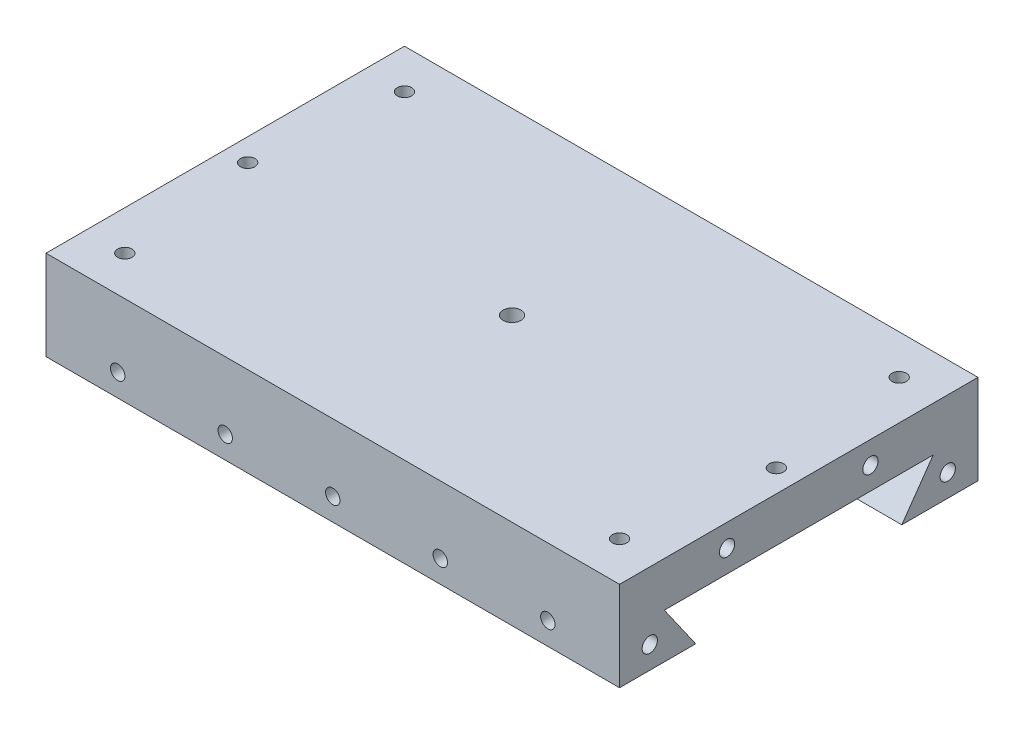
SolidWorks part; units mm, degrees
material "Ductile Iron"
ref_plane "Front Plane" through (0, 0, 0) normal (0, 0, 1) x (1, 0, 0)
ref_plane "Top Plane" through (0, 0, 0) normal (0, 1, 0) x (1, 0, 0)
ref_plane "Right Plane" through (0, 0, 0) normal (1, 0, 0) x (0, 0, -1)
sketch "Sketch1" plane through (0, 0, 0) normal (1, 0, 0) x (0, 0, -1)
  line L0 (0, 0) -> (26.9908, 0)
  line L1 (26.9908, 0) -> (15.875, 15.875)
  line L2 (15.875, 15.875) -> (111.125, 15.875)
  line L3 (111.125, 15.875) -> (100.0092, 0)
  line L4 (100.0092, 0) -> (127, 0)
  line L5 (127, 0) -> (127, 31.75)
  line L6 (127, 31.75) -> (0, 31.75)
  line L7 (0, 31.75) -> (0, 0)
  line L8 (0, 0) -> (-0.9069, 0.9069)
  dimension "D1" = 55
  dimension "D2" = 55
  dimension "D3" = 127
  dimension "D4" = 31.75
  dimension "D5" = 95.25
  dimension "D6" = 15.875
extrude "Boss-Extrude1" add sketch "Sketch1" along normal blind 203.2 contours L6 L7 L0 L1 L2 L3 L4 L5 region at (0, 19.6333, -63.5)
hole_wizard "1/4-20 Tapped Hole4" positions "Sketch12" profile "Sketch13" tap size "1/4-20" standard "ANSI Inch"
sketch "Sketch12" plane through (0, -44.45, -248.3324) normal (-1, 0, 0) x (0, 0, 1)
  line L0 (184.8324, 76.2) -> (184.8324, 60.325) construction
  line L3 (159.4324, 68.2625) -> (210.2324, 68.2625) construction
  line L4 (142.7653, 52.3875) -> (121.3324, 52.3875) construction
  line L7 (226.8995, 52.3875) -> (248.3324, 52.3875) construction
  point P0 (210.2324, 68.2625)
  point P22 (159.4324, 68.2625)
  point P23 (132.0489, 52.3875)
  point P24 (237.616, 52.3875)
sketch "Sketch13" plane through (0, 23.8125, -38.1) normal (0, 1, 0) x (0, 0, 1)
  line L0 (0, 0) -> (0, 18.0438)
  line L1 (0, 18.0438) -> (2.5527, 16.51)
  line L2 (2.5527, 16.51) -> (2.5527, 0)
  line L3 (2.5527, 0) -> (0, 0)
  line L4 (0, 18.0438) -> (-2.5527, 16.51) construction
  line L5 (0, -6.35) -> (0, 107.95) construction
  dimension "Tap Drill Dia." = 5.1054
  dimension "Tap Drill Depth" = 16.51
  dimension "Drill Angle" = 118
cosmetic thread "Hole Thread19" parameters "D1"=12.7, "D2"=6.35
cosmetic thread "Hole Thread20" parameters "D1"=12.7, "D2"=6.35
cosmetic thread "Hole Thread35" parameters "D1"=12.7, "D2"=6.35
cosmetic thread "Hole Thread36" parameters "D1"=12.7, "D2"=6.35
hole_wizard "1/4-28 Tapped Hole1" positions "Sketch14" profile "Sketch15" tap size "1/4-28" standard "ANSI Inch"
sketch "Sketch14" plane through (203.2, -44.45, -248.3324) normal (1, 0, 0) x (0, 0, -1)
  point P0 (-159.4324, 68.2625)
  point P1 (-210.2324, 68.2625)
  point P2 (-237.616, 52.3875)
  point P3 (-132.0489, 52.3875)
sketch "Sketch15" plane through (203.2, 23.8125, -88.9) normal (0, 1, 0) x (0, 0, -1)
  line L0 (0, 0) -> (0, 17.1194)
  line L1 (0, 17.1194) -> (2.7051, 15.494)
  line L2 (2.7051, 15.494) -> (2.7051, 0)
  line L3 (2.7051, 0) -> (0, 0)
  line L4 (0, 17.1194) -> (-2.7051, 15.494) construction
  line L5 (0, -6.35) -> (0, 107.95) construction
  dimension "Tap Drill Dia." = 5.4102
  dimension "Tap Drill Depth" = 15.494
  dimension "Drill Angle" = 118
cosmetic thread "Hole Thread31" parameters "D1"=12.7, "D2"=6.35
cosmetic thread "Hole Thread34" parameters "D1"=12.7, "D2"=6.35
cosmetic thread "Hole Thread37" parameters "D1"=12.7, "D2"=6.35
cosmetic thread "Hole Thread38" parameters "D1"=12.7, "D2"=6.35
hole_wizard "1/4-20 Tapped Hole5" positions "Sketch16" profile "Sketch17" tap size "1/4-20" standard "ANSI Inch"
sketch "Sketch16" plane through (0, 31.75, 0) normal (0, 1, 0) x (1, 0, 0)
  line L0 (189.23, 113.03) -> (189.23, 13.97) construction
  line L1 (187.325, 63.5) -> (203.2, 63.5) construction
  line L4 (41.4707, 127) -> (161.7293, 127) construction
  line L5 (101.6, 127) -> (101.6, 0) construction
  arc A1 (161.7293, 2.3997) -> (161.7293, 124.6003) centre (101.6, 63.5) ccw construction
  point P0 (189.23, 13.97)
  point P2 (195.2625, 63.5)
  point P4 (189.23, 113.03)
  point P30 (13.97, 113.03)
  point P31 (7.9375, 63.5)
  point P32 (13.97, 13.97)
cosmetic thread "Hole Thread39" parameters "D1"=8.89, "D2"=6.35
cosmetic thread "Hole Thread40" parameters "D1"=8.89, "D2"=6.35
cosmetic thread "Hole Thread41" parameters "D1"=8.89, "D2"=6.35
cosmetic thread "Hole Thread42" parameters "D1"=8.89, "D2"=6.35
cosmetic thread "Hole Thread43" parameters "D1"=8.89, "D2"=6.35
cosmetic thread "Hole Thread44" parameters "D1"=8.89, "D2"=6.35
sketch "Sketch17" plane through (189.23, 31.75, -13.97) normal (1, 0, 0) x (0, 0, 1)
  line L0 (0, 0) -> (0, 11.6938)
  line L1 (0, 11.6938) -> (2.5527, 10.16)
  line L2 (2.5527, 10.16) -> (2.5527, 0)
  line L5 (2.5527, 0) -> (0, 0)
  line L10 (0, 11.6938) -> (-2.5527, 10.16) construction
  line L11 (0, -6.35) -> (0, 107.95) construction
  dimension "Tap Drill Dia." = 5.1054
  dimension "Tap Drill Depth" = 10.16
  dimension "Drill Angle" = 118
hole_wizard "1/4 (0.25) Clearance Dowel Hole1" positions "Sketch18" profile "Sketch19" hole size "1/4" standard "ANSI Inch"
sketch "Sketch18" plane through (39.9328, 31.75, 145.9096) normal (0, 1, 0) x (1, 0, 0)
  point P0 (61.6672, 209.4096)
sketch "Sketch19" plane through (101.6, 31.75, -63.5) normal (1, 0, 0) x (0, 0, 1)
  line L0 (0, 0) -> (0, 6.35)
  line L1 (0, 6.35) -> (3.175, 6.35)
  line L2 (3.175, 6.35) -> (3.175, 0)
  line L5 (3.175, 0) -> (0, 0)
  line L11 (0, -6.35) -> (0, 107.95) construction
  dimension "Thru Hole Dia." = 6.35
  dimension "Thru Hole Depth" = 6.35
hole_wizard "gib screw 1/4-20 Tapped Hole6" positions "Sketch23" profile "Sketch22" tap size "1/4-20" standard "ANSI Inch" end condition up to next
sketch "Sketch23" plane through (0, 0, 0) normal (0, 0, 1) x (1, 0, 0)
  line L0 (203.2, 15.875) -> (0, 15.875) construction
  line L1 (203.2, 15.875) -> (0, 15.875) construction
  line L2 (0, 7.9375) -> (203.2, 7.9375) construction
  line L3 (0, 31.75) -> (0, 0) construction
  line L4 (203.2, 31.75) -> (203.2, 0) construction
  line L5 (101.6, 15.875) -> (101.6, 0) construction
  line L6 (203.2, 0) -> (0, 0) construction
  line L7 (25.4, 7.9375) -> (63.5, 7.9375) construction
  point P2 (25.4, 7.9375)
  point P21 (101.6, 7.9375)
  point P24 (63.5, 7.9375)
  point P25 (101.6, 7.9375)
  point P26 (139.7, 7.9375)
  point P27 (177.8, 7.9375)
  dimension "D2" = 38.1
  dimension "D1" = 5
sketch "Sketch22" plane through (25.4, 7.9375, 0) normal (1, 0, 0) x (0, -1, 0)
  line L0 (0, 0) -> (0, 21.4329)
  line L1 (0, 21.4329) -> (2.5527, 21.4329)
  line L2 (2.5527, 21.4329) -> (2.5527, 0)
  line L5 (2.5527, 0) -> (0, 0)
  line L11 (0, -6.35) -> (0, 107.95) construction
  dimension "Thru Tap Drill Dia." = 5.1054
  dimension "Thru Tap Drill Depth" = 21.4329
cosmetic thread "Hole Thread45" parameters "D2"=6.35
cosmetic thread "Hole Thread46" parameters "D2"=6.35
cosmetic thread "Hole Thread47" parameters "D2"=6.35
cosmetic thread "Hole Thread48" parameters "D2"=6.35
cosmetic thread "Hole Thread49" parameters "D2"=6.35
equation "\"dovetail-angle\" = 55"
equation "\"dovetail-stock-width\" = 5"
equation "\"dovetail-stock-height\" = 1.25"
equation "\"dovetail-depth\" = 0.5 * \"dovetail-stock-height\""
equation "\"dovetail-throat-width\" = \"dovetail-stock-width\" - (2 * \"dovetail-depth\")"
equation "\"delta-x\" = 6"
equation "\"delta-y\" = 3"
equation "\"delta-z\"= 2.5"
equation "\"acme-nut-height\"= 0.5"
equation "\"acme-nut-width\"= 0.75"
equation "\"gib-thickness\" = 0.25"
equation "\"x-slide-length\" = \"dovetail-stock-width\" + \"delta-x\""
equation "\"y-slide-length\" = \"dovetail-stock-width\" + \"delta-y\""
equation "\"dog-point-diam\" = .149"
equation "\"dog-point-length\" = .067"
equation "\"dovetail-double-height\" = 2 * \"dovetail-depth\" + 0.5"
equation "\"D1@Sketch1\"=\"dovetail-angle\""
equation "\"D2@Sketch1\"=\"dovetail-angle\""
equation "\"D3@Sketch1\"=\"dovetail-stock-width\""
equation "\"D4@Sketch1\"=\"dovetail-stock-height\""
equation "\"D5@Sketch1\"=\"dovetail-throat-width\""
equation "\"D6@Sketch1\"=\"dovetail-depth\""
equation "\"D1@Boss-Extrude1\"=\"y-slide-length\""
equation "\"acme-major-diam\" = .5"
equation "\"acme-pitch-diam\" = 0.45"
equation "\"acme-minor-diam\" = 0.4"
equation "\"acme-nut-od\" = 1.47"
equation "\"acme-nut-length\" = 1"
equation "\"acme-nut-trim-height\" = .75"
equation "\"screw-bearing-od\" = 0.5"
equation "\"screw-bearing-length\" = .25"
equation "\"screw-bearing-id\" = .375"
equation "\"end-plate-thickness\" = \"screw-bearing-length\""
equation "\"screw-add-length\" = 2 * \"end-plate-thickness\" + 1 + 0.5"
equation "\"x-screw-length\" = \"x-slide-length\" + \"screw-add-length\""
equation "\"y-screw-length\" = \"y-slide-length\" + \"screw-add-length\""
equation "\"acme-nut-mount-hole-space-horz\" = 0.82"
equation "\"acme-nut-mount-hole-space-vert\" = 0.5 * \"acme-nut-length\""
equation "\"vise-hole-center-dist\" = 6.75"
